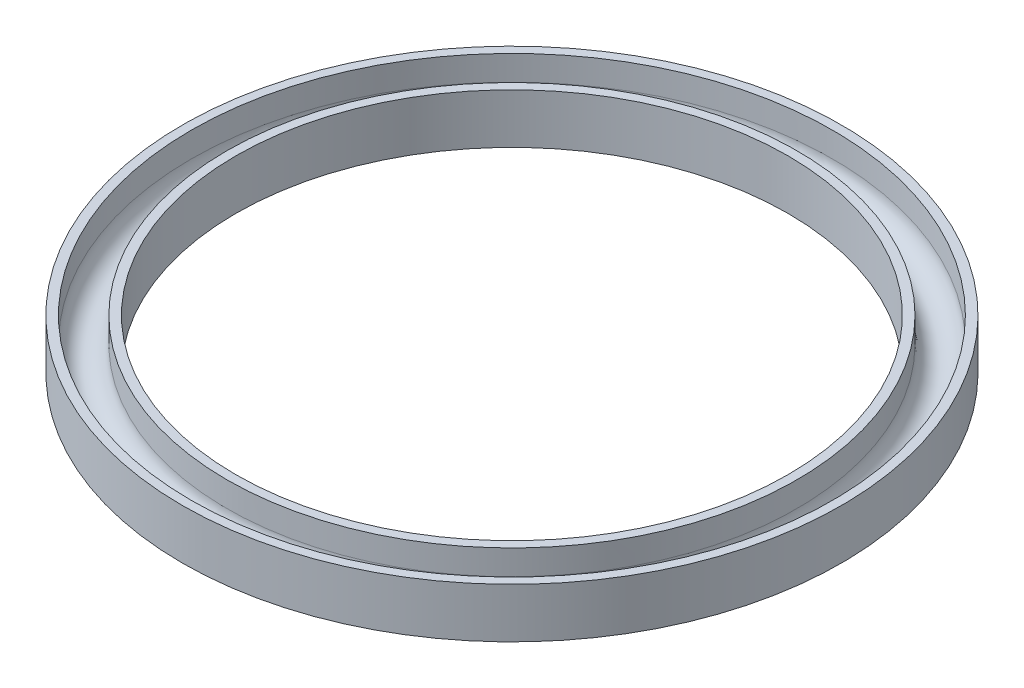
SolidWorks part; units mm, degrees
ref_plane "前视基准面" through (0, 0, 0) normal (0, 0, 1) x (1, 0, 0)
ref_plane "上视基准面" through (0, 0, 0) normal (0, 1, 0) x (1, 0, 0)
ref_plane "右视基准面" through (0, 0, 0) normal (1, 0, 0) x (0, 0, -1)
other "Configuration Table"
sketch "草图1" plane through (0, 0, 0) normal (0, 1, 0) x (1, 0, 0)
  circle A0 centre (0, 0) radius 80
  circle A1 centre (0, 0) radius 90
  circle A2 centre (0, 0) radius 77.5
  circle A3 centre (0, 0) radius 92.5
  dimension "D1" = 180
  dimension "D2" = 160
  dimension "D3" = 155
  dimension "D4" = 185
extrude "凸台-拉伸1" add sketch "草图1" along normal blind 7 contours A1 A0 region at (-87.4544, 0, 0)
extrude "凸台-拉伸2" add sketch "草图1<3>" along normal blind 14 contours A3 A1 | A0 A2 region at (-77.7373, 0, 0) region at (-92.2384, 0, 0)
sketch "草图1<3>" plane through (0, 0, 0) normal (0, 1, 0) x (1, 0, 0) same geometry as "草图1"
sketch "草图2" plane through (0, 0, 0) normal (0, 0, 1) x (1, 0, 0)
  line L0 (-90, 7) -> (-80, 7)
  line L1 (90, 7) -> (-90, 7) construction
  line L2 (80, 7) -> (-80, 7) construction
  arc A0 (-90, 7) -> (-80, 7) centre (-85, 7) ccw
ref_plane "基准面1" through (0, 7, 0) normal (0, 1, 0) x (1, 0, 0)
sketch "草图3" plane through (0, 7, 0) normal (0, 1, 0) x (1, 0, 0)
  circle A0 centre (0, 0) radius 85
  dimension "D1" = 170
sweep "切除-扫描1" cut profiles "草图2" path "草图3"
